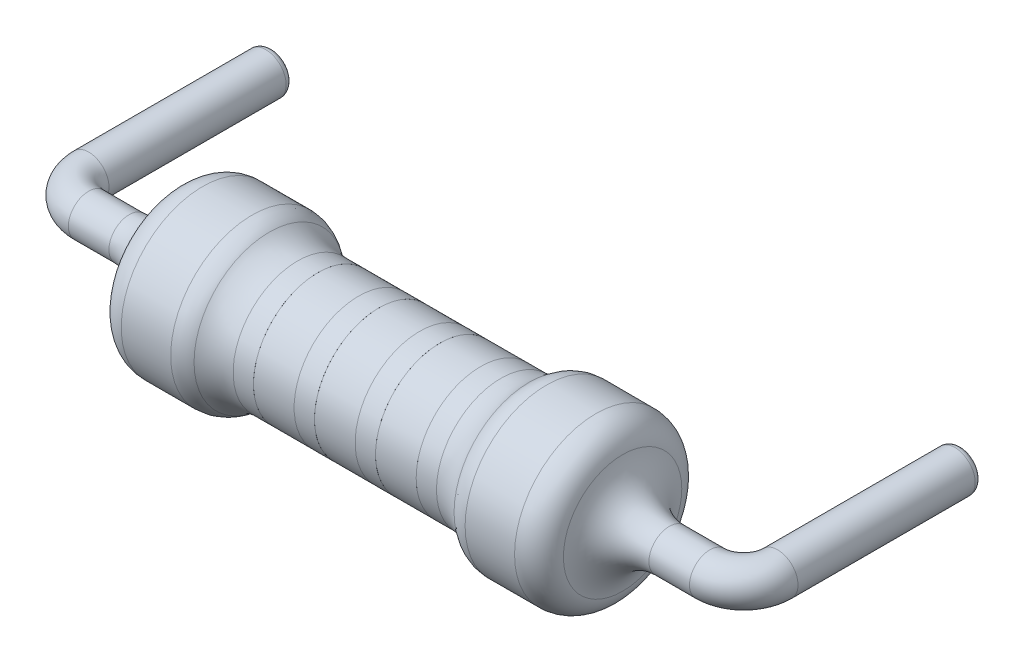
SolidWorks part; units mm, degrees
note: The reader was unsure of these and kept them because the rebuilt part matched: shared geometry of "Çizim4<3>", "Çizim4<4>", "Çizim4<5>", "Çizim4<7>", "Çizim4<9>", "Çizim4<10>".
ref_plane "Ön Düzlem" through (0, 0, 0) normal (0, 0, 1) x (1, 0, 0)
ref_plane "Üst Düzlem" through (0, 0, 0) normal (0, 1, 0) x (1, 0, 0)
ref_plane "Sağ Düzlem" through (0, 0, 0) normal (1, 0, 0) x (0, 0, -1)
ref_plane "Düzlem1" through (0, 0, -2) normal (0, 0, -1) x (-1, 0, 0)
sketch "Çizim2" plane through (0, 0, -2) normal (0, 0, -1) x (-1, 0, 0)
  line L0 (-5.08, 0) -> (5.08, 0) construction
  circle A0 centre (-5.08, 0) radius 0.3
  dimension "D2" = 0.6
  dimension "D1" = 10.16
sketch "Çizim3" plane through (0, 0, 0) normal (0, 1, 0) x (1, 0, 0)
  line L0 (5.08, 2) -> (5.08, -0.713)
  line L1 (4.58, -1.213) -> (-4.58, -1.213)
  line L2 (-5.08, -0.713) -> (-5.08, 2)
  line L3 (5.08, 2) -> (-5.08, 2) construction
  line L4 (55, 2) -> (-55, 2) construction
  arc A0 (-4.58, -1.213) -> (-5.08, -0.713) centre (-4.58, -0.713) cw
  arc A1 (5.08, -0.713) -> (4.58, -1.213) centre (4.58, -0.713) cw
  point P12 (5.08, 2)
  dimension "D2" = 0.5
  dimension "D1" = 3.213
sweep "Süpür2" add profiles "Çizim2" path "Çizim3"
fillet "Radyus4" radius 0.1 2 edges at (-4.78, 0, -2) (4.78, 0, -2)
sketch "Çizim4" plane through (0, 0, 0) normal (1, 0, 0) x (0, 0, -1)
  circle A0 centre (-1.213, 0) radius 1.2
  circle A1 centre (-1.213, 0) radius 0.95
  circle A2 centre (-1.213, 0) radius 0.9
  dimension "D1" = 2.4
  dimension "D2" = 1.9
  dimension "D3" = 1.8
extrude "Yükseklik-Ekstrüzyon2" add sketch "Çizim4" along normal mid plane 1.5 from offset 2.55 contours A0
extrude "Yükseklik-Ekstrüzyon3" add sketch "Çizim4<3>" against normal mid plane 1.5 from offset 2.55 contours A0 offset against normal yes
sketch "Çizim4<3>" plane through (0, 0, 0) normal (1, 0, 0) x (0, 0, -1) same geometry as "Çizim4"
extrude "Yükseklik-Ekstrüzyon4" add sketch "Çizim4<4>" along normal up to surface and the other way up to surface contours A1 up to face at (1.8, 0, 0.013) other way up to face at (-1.8, 0, 0.013)
sketch "Çizim4<4>" plane through (0, 0, 0) normal (1, 0, 0) x (0, 0, -1) same geometry as "Çizim4"
fillet "Radyus1" radius 0.4 4 edges at (3.3, 0, 0.013) (-3.3, 0, 0.013) (1.8, 0, 0.013) (-1.8, 0, 0.013)
fillet "Radyus2" radius 0.7 2 edges at (3.3, 0, 0.913) (-3.3, 0, 0.913)
fillet "Radyus3" radius 0.7 2 edges at (-1.8, 0, 0.263) (1.8, 0, 0.263)
extrude "Ekstrüzyon-İnce1" add sketch "Çizim4<5>" along normal blind 0.3 from offset 1.2 thin contours A2
sketch "Çizim4<5>" plane through (0, 0, 0) normal (1, 0, 0) x (0, 0, -1) same geometry as "Çizim4"
extrude "Ekstrüzyon-İnce2" add sketch "Çizim4<7>" along normal blind 0.3 from offset 0.3 thin contours A2
sketch "Çizim4<7>" plane through (0, 0, 0) normal (1, 0, 0) x (0, 0, -1) same geometry as "Çizim4"
extrude "Ekstrüzyon-İnce3" add sketch "Çizim4<9>" against normal blind 0.3 from offset 0.3 thin contours A2 offset against normal yes
sketch "Çizim4<9>" plane through (0, 0, 0) normal (1, 0, 0) x (0, 0, -1) same geometry as "Çizim4"
extrude "Ekstrüzyon-İnce4" add sketch "Çizim4<10>" against normal blind 0.3 from offset 1.2 thin contours A2 offset against normal yes
sketch "Çizim4<10>" plane through (0, 0, 0) normal (1, 0, 0) x (0, 0, -1) same geometry as "Çizim4"
